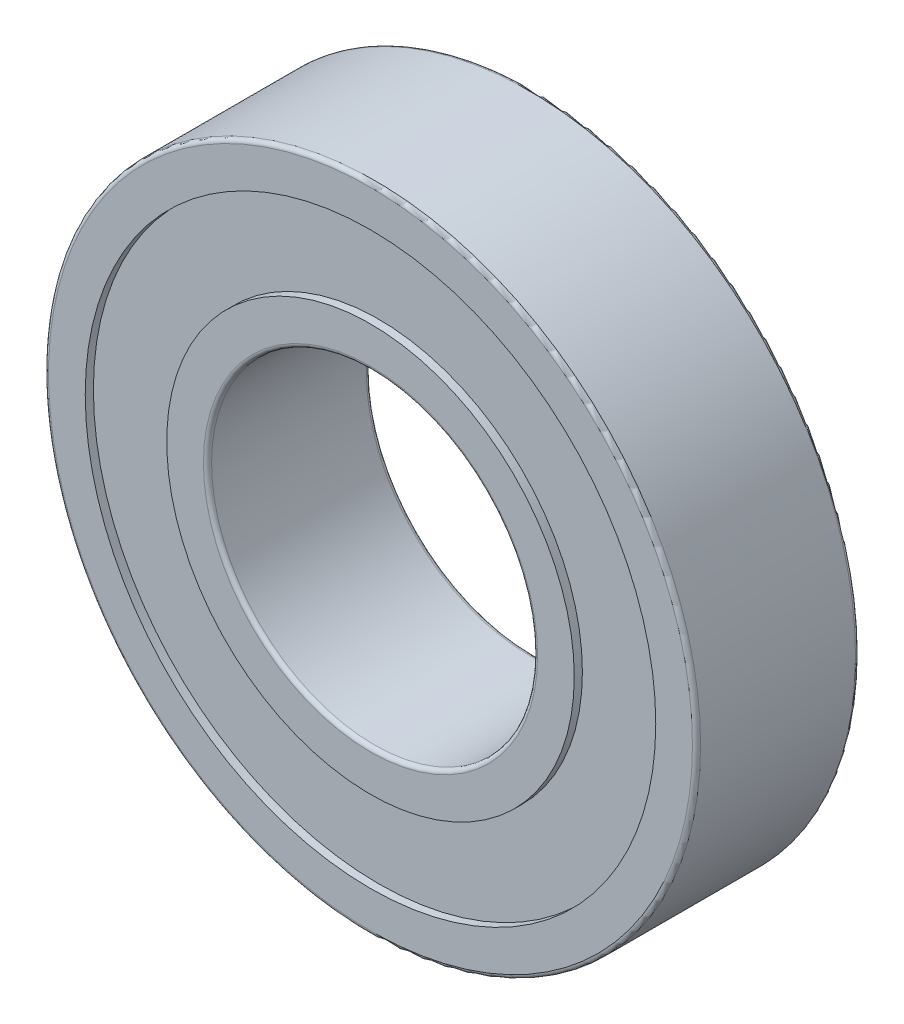
SolidWorks part; units mm, degrees
ref_plane "Front Plane" through (0, 0, 0) normal (0, 0, 1) x (1, 0, 0)
ref_plane "Top Plane" through (0, 0, 0) normal (0, 1, 0) x (1, 0, 0)
ref_plane "Right Plane" through (0, 0, 0) normal (1, 0, 0) x (0, 0, -1)
sketch "Sketch1" plane through (0, 0, 0) normal (0, 0, 1) x (1, 0, 0)
  circle A0 centre (0, 0) radius 6
  circle A1 centre (0, 0) radius 12
  dimension "D1" = 12
  dimension "D2" = 24
extrude "Boss-Extrude1" add sketch "Sketch1" along normal blind 6
sketch "Sketch2" plane through (0, 0, 6) normal (0, 0, 1) x (1, 0, 0)
  circle A2 centre (0, 0) radius 10.5
  circle A3 centre (0, 0) radius 10.5
  circle A5 centre (0, 0) radius 7.5
  circle A6 centre (0, 0) radius 7.5
  dimension "D1" = 1.5
  dimension "D2" = 1.5
extrude "Cut-Extrude1" cut sketch "Sketch2" against normal blind 0.3
extrude "Cut-Extrude2" cut sketch "Sketch2<2>" along normal blind 0.5 from surface starting at face at (12, 0, 0)
sketch "Sketch2<2>" plane through (0, 0, 6) normal (0, 0, 1) x (1, 0, 0) same geometry as "Sketch2"
fillet "Fillet1" radius 0.15 4 edges at (6, 0, 6) (12, 0, 6) (6, 0, 0) (12, 0, 0)
